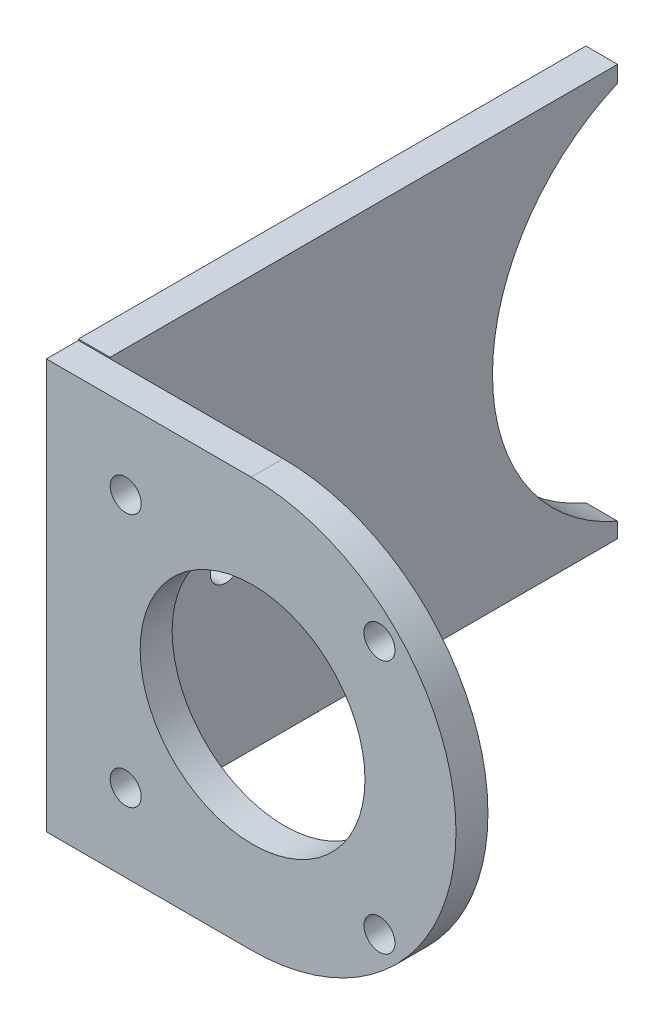
SolidWorks part; units mm, degrees
ref_plane "Front" through (0, 0, 0) normal (0, 0, 1) x (1, 0, 0)
ref_plane "Top" through (0, 0, 0) normal (0, 1, 0) x (1, 0, 0)
ref_plane "Right" through (0, 0, 0) normal (1, 0, 0) x (0, 0, -1)
sketch "Sketch1" plane through (0, 0, 0) normal (0, 0, 1) x (1, 0, 0)
  line L0 (1.5871, 42.7378) -> (1.5875, 22.5718)
  line L4 (22.0848, 42.7382) -> (1.5871, 42.7378)
  line L6 (1.5875, 22.5718) -> (1.5875, 1.7382)
  line L7 (1.5875, 1.7382) -> (22.0855, 1.7382)
  arc A0 (22.0855, 1.7382) -> (22.0848, 42.7382) centre (22.0852, 22.2382) ccw
extrude "Extrude1" add sketch "Sketch1" along normal blind 3.2
sketch "Sketch2" plane through (0, 0, 3.2) normal (0, 0, 1) x (1, 0, 0)
  circle A0 centre (22.225, 22.225) radius 11.25
extrude "Cut-Extrude1" cut sketch "Sketch2" against normal through all
sketch "Sketch3" plane through (0, 0, 3.2) normal (0, 0, 1) x (1, 0, 0)
  circle A0 centre (34.925, 34.925) radius 1.55
  circle A1 centre (9.525, 34.925) radius 1.55
  circle A2 centre (34.925, 9.525) radius 1.55
  circle A3 centre (9.525, 9.525) radius 1.55
extrude "Cut-Extrude2" cut sketch "Sketch3" against normal through all
sketch "Sketch5" plane through (0, 0, 0) normal (0, 0, -1) x (-1, 0, 0)
  line L1 (-1.5875, 1.7382) -> (-4.7625, 1.7382)
  line L2 (-1.5875, 1.7382) -> (-1.5875, 42.8625)
  line L3 (-1.5875, 42.8625) -> (-4.7625, 42.8625)
  line L4 (-4.7625, 1.7382) -> (-4.7625, 42.8625)
extrude "Extrude3" add sketch "Sketch5" along normal blind 50.8
sketch "Sketch6" plane through (4.7625, 0, 0) normal (1, 0, 0) x (0, 0, -1)
  circle A0 centre (58.9125, 22.2382) radius 20.6375
  circle A1 centre (5.225, 25.4132) radius 1.55
  circle A2 centre (11.575, 19.0632) radius 1.55
extrude "Cut-Extrude3" cut sketch "Sketch6" against normal through all
